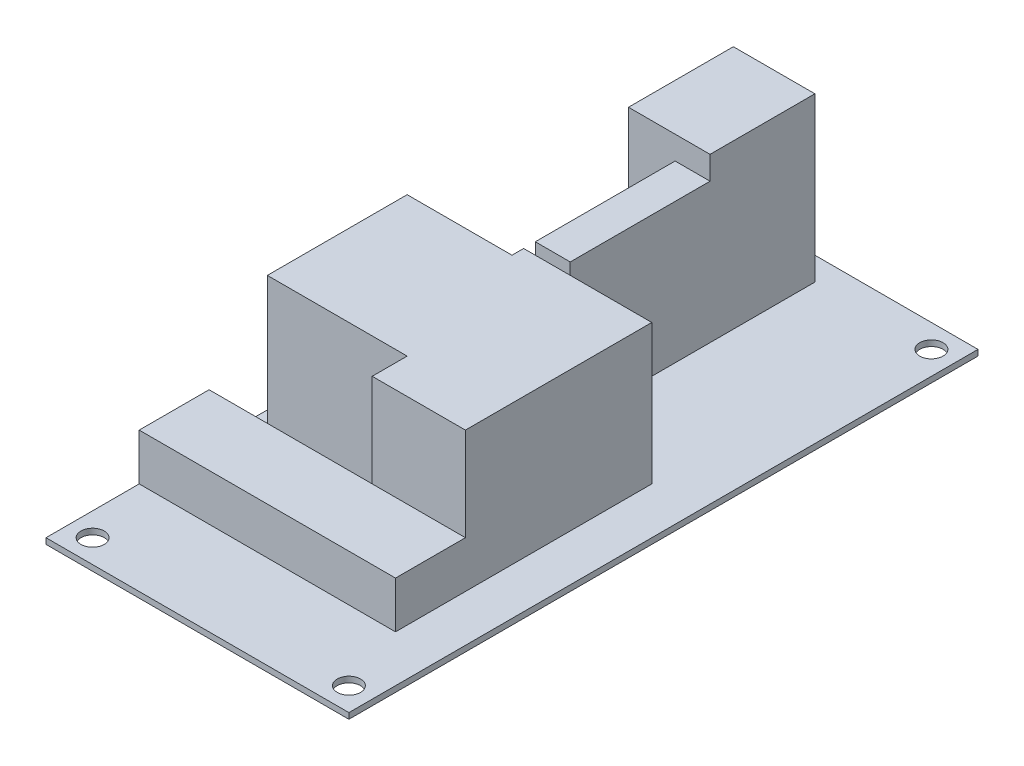
SolidWorks part; units mm, degrees
ref_plane "Front Plane" through (0, 0, 0) normal (0, 0, 1) x (1, 0, 0)
ref_plane "Top Plane" through (0, 0, 0) normal (0, 1, 0) x (1, 0, 0)
ref_plane "Right Plane" through (0, 0, 0) normal (1, 0, 0) x (0, 0, -1)
sketch "Sketch1" plane through (0, 0, 0) normal (0, 1, 0) x (1, 0, 0)
  line L1 (-20.6375, 42.8625) -> (20.6375, 42.8625)
  line L2 (-20.6375, 42.8625) -> (-20.6375, -42.8625)
  line L3 (-20.6375, -42.8625) -> (20.6375, -42.8625)
  line L4 (20.6375, 42.8625) -> (20.6375, -42.8625)
  line L5 (-20.6375, 42.8625) -> (20.6375, -42.8625) construction
  line L6 (-20.6375, -42.8625) -> (20.6375, 42.8625) construction
  point P0 (0, 0)
  dimension "D1" = 85.725
  dimension "D2" = 41.275
extrude "Boss-Extrude1" add sketch "Sketch1" along normal blind 0.7937
sketch "Sketch2" plane through (0, 0.7937, 0) normal (0, 1, 0) x (1, 0, 0)
  line L0 (-20.6375, 42.8625) -> (-20.6375, -42.8625) construction
  line L1 (-20.6375, -30.1625) -> (14.2875, -30.1625)
  line L2 (-20.6375, -30.1625) -> (-20.6375, -20.6375)
  line L3 (-20.6375, -20.6375) -> (14.2875, -20.6375)
  line L4 (14.2875, -30.1625) -> (14.2875, -20.6375)
  line L5 (-20.6375, -42.8625) -> (20.6375, -42.8625) construction
  dimension "D1" = 34.925
  dimension "D2" = 12.7
  dimension "D3" = 9.525
extrude "Boss-Extrude2" add sketch "Sketch2" along normal blind 6.35
sketch "Sketch3" plane through (0, 0.7937, 0) normal (0, 1, 0) x (1, 0, 0)
  line L0 (14.2875, -20.6375) -> (14.2875, 4.7625)
  line L1 (14.2875, 4.7625) -> (-3.175, 4.7625)
  line L2 (-3.175, 4.7625) -> (-3.175, 3.175)
  line L3 (-3.175, 3.175) -> (-17.4625, 3.175)
  line L4 (-17.4625, 3.175) -> (-17.4625, -15.875)
  line L5 (-17.4625, -15.875) -> (1.5875, -15.875)
  line L6 (1.5875, -15.875) -> (1.5875, -20.6375)
  line L7 (14.2875, -20.6375) -> (-20.6375, -20.6375) construction
  line L8 (1.5875, -20.6375) -> (14.2875, -20.6375)
  point P11 (1.5875, -17.8827)
  dimension "D1" = 17.4625
  dimension "D2" = 1.5875
  dimension "D3" = 14.2875
  dimension "D4" = 19.05
  dimension "D5" = 12.7
  dimension "D6" = 4.7625
extrude "Boss-Extrude3" add sketch "Sketch3" along normal blind 19.05
sketch "Sketch4" plane through (0, 0.7937, 0) normal (0, 1, 0) x (1, 0, 0)
  line L1 (-14.2875, 9.525) -> (-3.175, 9.525)
  line L2 (-14.2875, 9.525) -> (-14.2875, 20.6375)
  line L3 (-14.2875, 20.6375) -> (-3.175, 20.6375)
  line L4 (-3.175, 9.525) -> (-3.175, 20.6375)
  line L5 (-3.175, 4.7625) -> (-3.175, 3.175) construction
  line L6 (-3.175, 3.175) -> (-17.4625, 3.175) construction
  dimension "D1" = 6.35
  dimension "D2" = 11.1125
  dimension "D3" = 11.1125
extrude "Boss-Extrude4" add sketch "Sketch4" along normal blind 6.35
sketch "Sketch5" plane through (0, 7.1437, 0) normal (0, 1, 0) x (1, 0, 0)
  line L0 (-3.175, 20.6375) -> (-14.2875, 20.6375) construction
  line L1 (-14.2875, 20.6375) -> (-14.2875, 9.525) construction
  circle A0 centre (-8.7313, 15.0812) radius 2.3813
  point P2 (0, 0)
  point P5 (-8.7313, 20.6375)
  point P6 (0, 0)
  point P9 (-14.2875, 15.0812)
  dimension "D1" = 4.7625
extrude "Boss-Extrude5" add sketch "Sketch5" along normal blind 3.175
sketch "Sketch6" plane through (0, 0.7937, 0) normal (0, 1, 0) x (1, 0, 0)
  line L0 (-3.175, 9.525) -> (-3.175, 20.6375) construction
  line L1 (-3.175, 6.35) -> (1.5875, 6.35)
  line L2 (-3.175, 6.35) -> (-3.175, 25.4)
  line L3 (-3.175, 25.4) -> (1.5875, 25.4)
  line L4 (1.5875, 6.35) -> (1.5875, 25.4)
  line L5 (14.2875, 4.7625) -> (-3.175, 4.7625) construction
  dimension "D1" = 1.5875
  dimension "D2" = 4.7625
  dimension "D3" = 19.05
extrude "Boss-Extrude6" add sketch "Sketch6" along normal blind 19.05
sketch "Sketch7" plane through (0, 0.7937, 0) normal (0, 1, 0) x (1, 0, 0)
  line L0 (-20.6375, 42.8625) -> (-20.6375, -20.6375) construction
  line L1 (-9.525, 25.4) -> (1.5875, 25.4)
  line L2 (-9.525, 25.4) -> (-9.525, 39.6875)
  line L3 (-9.525, 39.6875) -> (1.5875, 39.6875)
  line L4 (1.5875, 25.4) -> (1.5875, 39.6875)
  line L5 (20.6375, 42.8625) -> (-20.6375, 42.8625) construction
  line L6 (1.5875, 6.35) -> (1.5875, 25.4) construction
  dimension "D1" = 11.1125
  dimension "D2" = 3.175
  dimension "D3" = 14.2875
extrude "Boss-Extrude7" add sketch "Sketch7" along normal blind 22.225
sketch "Sketch8" plane through (0, 0.7937, 0) normal (0, 1, 0) x (1, 0, 0)
  line L0 (-20.6375, 42.8625) -> (-20.6375, -20.6375) construction
  line L1 (-17.4625, -39.6875) -> (17.4625, -39.6875) construction
  line L2 (-17.4625, -39.6875) -> (-17.4625, 39.6875) construction
  line L3 (-17.4625, 39.6875) -> (17.4625, 39.6875) construction
  line L4 (17.4625, -39.6875) -> (17.4625, 39.6875) construction
  line L5 (20.6375, -42.8625) -> (20.6375, 42.8625) construction
  line L6 (20.6375, 42.8625) -> (-20.6375, 42.8625) construction
  line L7 (-20.6375, -42.8625) -> (20.6375, -42.8625) construction
  circle A3 centre (-17.4625, 39.6875) radius 1.5875
  circle A4 centre (17.4625, 39.6875) radius 1.5875
  circle A5 centre (-17.4625, -39.6875) radius 1.5875
  circle A6 centre (17.4625, -39.6875) radius 1.5875
  dimension "D5" = 3.175
  dimension "D1" = 3.175
  dimension "D2" = 3.175
  dimension "D3" = 3.175
  dimension "D4" = 3.175
extrude "Cut-Extrude1" cut sketch "Sketch8" against normal through all
